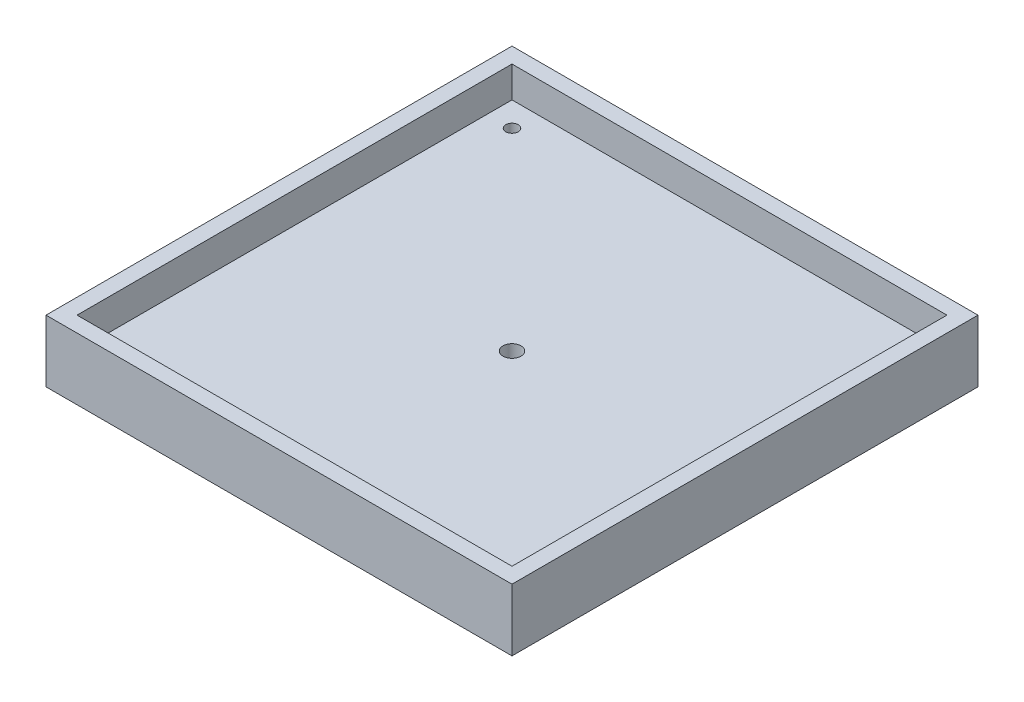
SolidWorks part; units mm, degrees
note: The reader was unsure of these and kept them because the rebuilt part matched: shared geometry of "Sketch1<3>", "Sketch1<4>", "Sketch1<5>".
ref_plane "Front Plane" through (0, 0, 0) normal (0, 0, 1) x (1, 0, 0)
ref_plane "Top Plane" through (0, 0, 0) normal (0, 1, 0) x (1, 0, 0)
ref_plane "Right Plane" through (0, 0, 0) normal (1, 0, 0) x (0, 0, -1)
sketch "Sketch1" plane through (0, 0, 0) normal (0, 1, 0) x (1, 0, 0)
  line L1 (-75, -75) -> (75, -75)
  line L2 (-75, -75) -> (-75, 75)
  line L3 (-75, 75) -> (75, 75)
  line L4 (75, -75) -> (75, 75)
  line L5 (-75, -75) -> (75, 75) construction
  line L6 (-75, 75) -> (75, -75) construction
  line L7 (-70, 70) -> (70, 70)
  line L8 (-70, 70) -> (-70, -70)
  line L9 (-70, -70) -> (70, -70)
  line L10 (70, 70) -> (70, -70)
  line L11 (-70, 70) -> (70, -70) construction
  line L12 (-70, -70) -> (70, 70) construction
  circle A0 centre (62.1, 62.1) radius 2
  circle A2 centre (62.1, -62.1) radius 2
  circle A3 centre (-62.1, -62.1) radius 2
  circle A4 centre (-62.1, 62.1) radius 2
  circle A5 centre (0, 0) radius 2.9
  circle A6 centre (0, 0) radius 57.5
  point P0 (0, 0)
  point P6 (0, 0)
  point P17 (0, 0)
  point P24 (0, 0)
  dimension "D4" = 4
  dimension "D9" = 5.8
  dimension "D10" = 115
  dimension "D1" = 150
  dimension "D2" = 150
  dimension "D3" = 140
  dimension "D5" = 12.9
  dimension "D7" = 12.9
  dimension "D8" = 12.9
  dimension "D6" = 4
extrude "Boss-Extrude1" add sketch "Sketch1" along normal blind 20 contours L1 L4 L3 L2 L7 L10 L9 L8
extrude "Boss-Extrude2" add sketch "Sketch1<3>" along normal blind 10 contours L10 L7 L8 L9 A5 A0 | A6
sketch "Sketch1<3>" plane through (0, 0, 0) normal (0, 1, 0) x (1, 0, 0) same geometry as "Sketch1"
extrude "Cut-Extrude1" cut sketch "Sketch1<4>" along normal blind 4 contours A6
sketch "Sketch1<4>" plane through (0, 0, 0) normal (0, 1, 0) x (1, 0, 0) same geometry as "Sketch1"
extrude "Cut-Extrude2" cut sketch "Sketch1<5>" along normal blind 10 contours A5
sketch "Sketch1<5>" plane through (0, 0, 0) normal (0, 1, 0) x (1, 0, 0) same geometry as "Sketch1"
